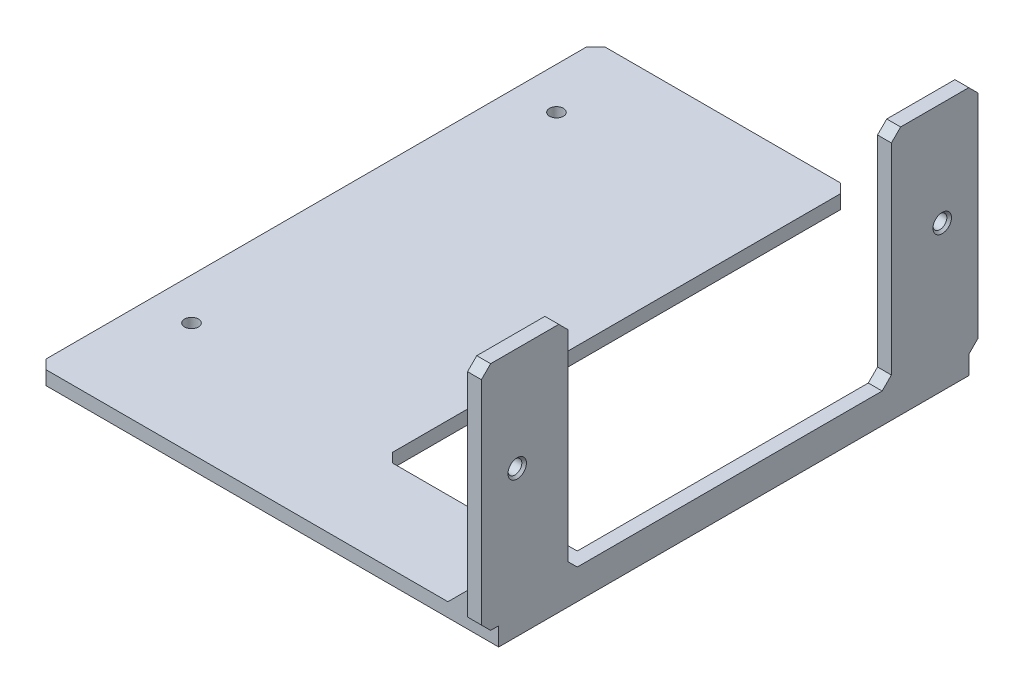
SolidWorks part; units mm, degrees
ref_plane "前视基准面" through (0, 0, 0) normal (0, 0, 1) x (1, 0, 0)
ref_plane "上视基准面" through (0, 0, 0) normal (0, 1, 0) x (1, 0, 0)
ref_plane "右视基准面" through (0, 0, 0) normal (1, 0, 0) x (0, 0, -1)
sketch "草图1" plane through (0, 0, 0) normal (1, 0, 0) x (0, 0, -1)
  line L1 (-53.75, 22.5) -> (53.75, 22.5)
  line L2 (-53.75, 22.5) -> (-53.75, -27.5)
  line L3 (-53.75, -27.5) -> (53.75, -27.5)
  line L4 (53.75, 22.5) -> (53.75, -27.5)
  dimension "D1" = 107.5
  dimension "D2" = 50
  dimension "D3" = 22.5
  dimension "D4" = 53.75
extrude "凸台-拉伸1" add sketch "草图1" along normal blind 3
chamfer "倒角1" distance 2 angle 45 4 edges at (1.5, -27.5, -53.75) (1.5, 22.5, -53.75) (1.5, -27.5, 53.75) (1.5, 22.5, 53.75)
sketch "草图3" plane through (3, 0, 0) normal (1, 0, 0) x (0, 0, -1)
  circle A0 centre (46, 0) radius 1.5
  circle A1 centre (-46, 0) radius 1.5
  dimension "D1" = 92
  dimension "D3" = 3
  dimension "D4" = 3
  dimension "D2" = 46
extrude "切除-拉伸1" cut sketch "草图3" against normal through all and the other way through all
chamfer "倒角2" distance 0.5 angle 45 2 edges at (3, 0, 44.5) (3, 0, -47.5)
sketch "草图4" plane through (3, 0, 0) normal (1, 0, 0) x (0, 0, -1)
  line L0 (-51.75, -27.5) -> (51.75, -27.5) construction
  line L1 (-50, -27.5) -> (-30, -27.5)
  line L2 (-50, -27.5) -> (-50, -28.5)
  line L3 (-50, -28.5) -> (-30, -28.5)
  line L4 (-30, -27.5) -> (-30, -28.5)
  dimension "D1" = 20
  dimension "D2" = 30
  dimension "D3" = 1
extrude "凸台-拉伸2" add sketch "草图4" against normal blind 3 separate body
sketch "草图5" plane through (0, -28.5, 0) normal (0, -1, 0) x (1, 0, 0)
  line L0 (0, 50) -> (3, 50) construction
  line L2 (3, 50) -> (3, 30)
  line L3 (3, 30) -> (-42, 30)
  line L5 (-42, 30) -> (-42, -71)
  line L6 (-97, 50) -> (3, 50)
  line L7 (-97, 50) -> (-97, -71)
  line L8 (-97, -71) -> (-42, -71)
  line L11 (0, 30) -> (3, 30) construction
  line L12 (3, 51.75) -> (3, -51.75) construction
  dimension "D1" = 100
  dimension "D2" = 45
  dimension "D3" = 55
  dimension "D5" = 101
extrude "凸台-拉伸3" add sketch "草图5" along normal blind 3
sketch "草图6" plane through (0, 0, 30) normal (0, 0, -1) x (-1, 0, 0)
  line L0 (0, -20.5) -> (8, -28.5)
  line L1 (0, -28.5) -> (0, -27.5) construction
  line L2 (42, -28.5) -> (0, -28.5) construction
  line L3 (8, -28.5) -> (0, -28.5)
  line L4 (0, -28.5) -> (0, -20.5)
  dimension "D1" = 8
  dimension "D2" = 8
extrude "凸台-拉伸4" add sketch "草图6" against normal blind 20
sketch "草图7" plane through (0, -28.5, 0) normal (0, 1, 0) x (1, 0, 0)
  circle A0 centre (-88, 53.5) radius 1.5
  circle A1 centre (-88, -25.5) radius 1.5
  dimension "D1" = 79
  dimension "D2" = 3
  dimension "D3" = 3
  dimension "D4" = 25.5
  dimension "D5" = 88
extrude "切除-拉伸2" cut sketch "草图7" against normal blind 30
combine bodies "组合1" operation type add bodies to combine 107 111
sketch "草图8" plane through (3, 0, 0) normal (1, 0, 0) x (0, 0, -1)
  line L0 (51.75, 22.5) -> (-51.75, 22.5) construction
  line L1 (-35, 22.5) -> (35, 22.5)
  line L2 (-35, 22.5) -> (-35, -25)
  line L3 (-35, -25) -> (35, -25)
  line L4 (35, 22.5) -> (35, -25)
  dimension "D1" = 70
  dimension "D2" = 35
  dimension "D3" = 25
extrude "切除-拉伸3" cut sketch "草图8" against normal blind 10
chamfer "倒角5" distance 2 angle 45 2 edges at (1.5, -25, -35) (-0.75, -25, 35)
chamfer "倒角6" distance 2 angle 45 2 edges at (1.5, 22.5, -35) (1.5, 22.5, 35)
chamfer "倒角7" distance 2 angle 45 4 edges at (-97, -30, 50) (-97, -30, -71) (-42, -30, -71) (-42, -30, 30)
sketch "草图9" plane through (0, -27.5, 0) normal (0, -1, 0) x (1, 0, 0)
  line L4 (3, -51.75) -> (3, 30)
  line L5 (3, 30) -> (0, 30)
  line L6 (0, 30) -> (0, -51.75)
  line L7 (0, -51.75) -> (3, -51.75)
  line L8 (3, -51.75) -> (3, 30)
  line L10 (0, 30) -> (0, -51.75)
  line L11 (0, -51.75) -> (3, -51.75)
  line L13 (3, 30) -> (0, 30)
  dimension "D1" = 0
extrude "凸台-拉伸5" add sketch "草图9" along normal up to surface (4 mm away) up to face at (-88, -31.5, -52)
